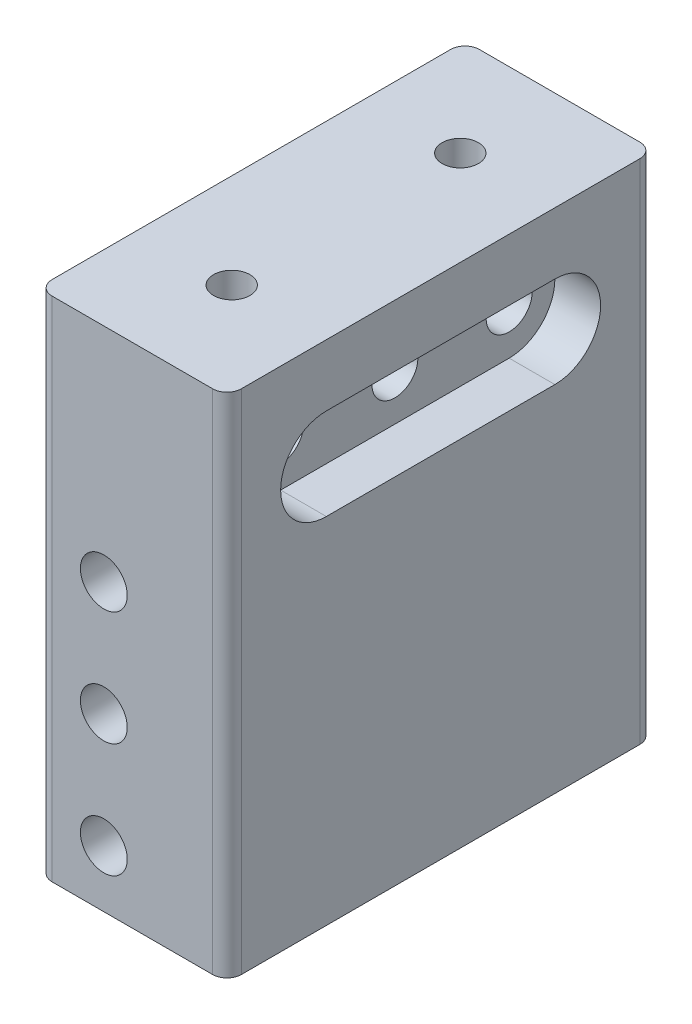
SolidWorks part; units mm, degrees
material "PET"
ref_plane "Front Plane" through (0, 0, 0) normal (0, 0, 1) x (1, 0, 0)
ref_plane "Top Plane" through (0, 0, 0) normal (0, 1, 0) x (1, 0, 0)
ref_plane "Right Plane" through (0, 0, 0) normal (1, 0, 0) x (0, 0, -1)
sketch "Sketch1" plane through (0, 0, 0) normal (0, 1, 0) x (1, 0, 0)
  line L1 (-10.5156, -23.7427) -> (10.5156, -23.7427)
  line L2 (-10.5156, -23.7427) -> (-10.5156, 23.7426)
  line L3 (-10.5156, 23.7426) -> (10.5156, 23.7426)
  line L4 (10.5156, -23.7427) -> (10.5156, 23.7426)
  line L5 (-10.5156, -23.7427) -> (10.5156, 23.7426) construction
  line L6 (-10.5156, 23.7426) -> (10.5156, -23.7427) construction
  point P0 (0, 0)
  dimension "D1" = 21.0312
  dimension "D2" = 47.4853
extrude "Boss-Extrude1" add sketch "Sketch1" along normal mid plane 50.8
sketch "Sketch2" plane through (0, 0, 23.7427) normal (0, 0, 1) x (1, 0, 0)
  line L5 (-10.5156, 25.4) -> (10.5156, 25.4) construction
  circle A1 centre (-3.175, -6.35) radius 2.6035
  circle A2 centre (-3.175, 6.35) radius 2.6035
  circle A3 centre (-3.175, -19.05) radius 2.6035
  dimension "D3" = 19.05
  dimension "D1" = 13.6906
  dimension "D2" = 5.207
  dimension "D4" = 12.7
  dimension "D5" = 12.7
extrude "Cut-Extrude1" cut sketch "Sketch2" against normal through all
sketch "Sketch4" plane through (10.5156, 0, 0) normal (1, 0, 0) x (0, 0, -1)
  line L0 (-23.7427, 25.4) -> (23.7426, 25.4) construction
  circle A0 centre (-12.7, 19.05) radius 2.5527
  circle A1 centre (12.7, 19.05) radius 2.5527
  circle A2 centre (0, 19.05) radius 2.5527
  dimension "D5" = 5.1054
  dimension "D1" = 6.35
  dimension "D3" = 12.7
  dimension "D4" = 12.7
extrude "Cut-Extrude3" cut sketch "Sketch4" against normal through all
fillet "Fillet1" radius 1.5875 4 edges at (10.5156, 0, 23.7427) (-10.5156, 0, 23.7427) (-10.5156, 0, -23.7426) (10.5156, 0, -23.7426)
sketch "Sketch7" plane through (10.5156, 0, 0) normal (1, 0, 0) x (0, 0, -1)
  line L0 (-12.7, 19.05) -> (12.7, 19.05) construction
  line L1 (-12.7, 24.13) -> (12.7, 24.13)
  line L2 (-12.7, 13.97) -> (12.7, 13.97)
  arc A0 (-12.7, 24.13) -> (-12.7, 13.97) centre (-12.7, 19.05) ccw
  arc A1 (12.7, 13.97) -> (12.7, 24.13) centre (12.7, 19.05) ccw
  point P4 (0, 19.05)
  dimension "D1" = 5.08
extrude "Cut-Extrude5" cut sketch "Sketch7" against normal blind 5.08
sketch "Sketch8" plane through (0, 25.4, 0) normal (0, 1, 0) x (1, 0, 0)
  line L4 (-8.9281, -23.7427) -> (8.9281, -23.7427)
  line L5 (10.5156, -22.1552) -> (10.5156, 22.1551)
  line L6 (8.9281, 23.7426) -> (-8.9281, 23.7426)
  line L7 (-10.5156, 22.1551) -> (-10.5156, -22.1552)
  line L8 (-8.9281, -23.7427) -> (8.9281, -23.7427)
  line L9 (10.5156, -22.1552) -> (10.5156, 22.1551)
  line L10 (8.9281, 23.7426) -> (-8.9281, 23.7426)
  line L11 (-10.5156, 22.1551) -> (-10.5156, -22.1552)
  arc A4 (8.9281, -23.7427) -> (10.5156, -22.1552) centre (8.9281, -22.1552) ccw
  arc A5 (10.5156, 22.1551) -> (8.9281, 23.7426) centre (8.9281, 22.1551) ccw
  arc A6 (-8.9281, 23.7426) -> (-10.5156, 22.1551) centre (-8.9281, 22.1551) ccw
  arc A7 (-8.9281, 23.7426) -> (-10.5156, 22.1551) centre (-8.9281, 22.1551) ccw
  arc A8 (8.9281, -23.7427) -> (10.5156, -22.1552) centre (8.9281, -22.1552) ccw
  arc A9 (10.5156, 22.1551) -> (8.9281, 23.7426) centre (8.9281, 22.1551) ccw
  arc A10 (-10.5156, -22.1552) -> (-8.9281, -23.7427) centre (-8.9281, -22.1552) ccw
  arc A11 (-10.5156, -22.1552) -> (-8.9281, -23.7427) centre (-8.9281, -22.1552) ccw
  dimension "D1" = 0
extrude "Boss-Extrude2" add sketch "Sketch8" along normal blind 5.588
sketch "Sketch9" plane through (0, 30.988, 0) normal (0, 1, 0) x (1, 0, 0)
  line L0 (-10.5156, 0) -> (10.5156, 0) construction
  line L1 (-10.5156, 22.1551) -> (-10.5156, -22.1552) construction
  line L2 (10.5156, -22.1552) -> (10.5156, 22.1551) construction
  circle A0 centre (0, 12.7) radius 2.0193
  circle A2 centre (0, -12.7) radius 2.0193
  dimension "D2" = 4.0386
  dimension "D1" = 12.7
  dimension "D3" = 10.5156
extrude "Cut-Extrude6" cut sketch "Sketch9" against normal blind 5.08
